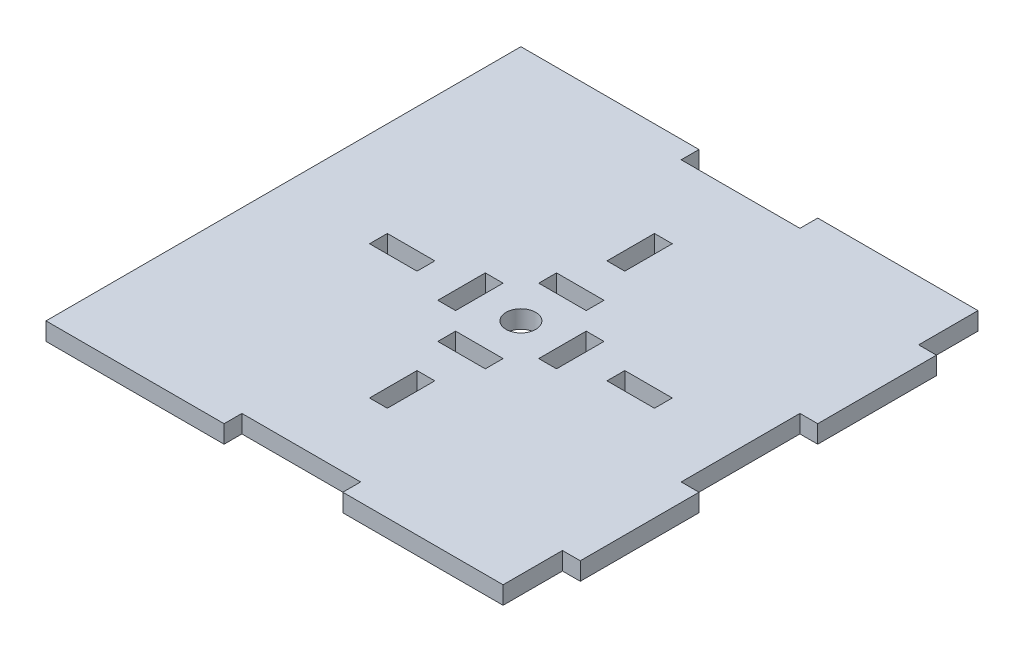
SolidWorks part; units mm, degrees
ref_plane "Alzado" through (0, 0, 0) normal (0, 0, 1) x (1, 0, 0)
ref_plane "Planta" through (0, 0, 0) normal (0, 1, 0) x (1, 0, 0)
ref_plane "Vista lateral" through (0, 0, 0) normal (1, 0, 0) x (0, 0, -1)
sketch "Croquis1" plane through (0, 0, 0) normal (0, 1, 0) x (1, 0, 0)
  line L0 (0, 0) -> (0, 10) construction
  line L1 (-40, 40) -> (-10, 40)
  line L2 (-40, 40) -> (-40, -40)
  line L3 (-40, -40) -> (-10, -40)
  line L4 (37, 30) -> (40, 30)
  line L5 (-40, 40) -> (40, -40) construction
  line L6 (-40, -40) -> (40, 40) construction
  line L7 (0, 10) -> (-4, 10)
  line L8 (-4, 10) -> (-4, 7)
  line L9 (-4, 7) -> (4, 7)
  line L10 (4, 7) -> (4, 10)
  line L11 (4, 10) -> (0, 10)
  line L12 (7, 4) -> (7, -4)
  line L13 (7, -4) -> (10, -4)
  line L14 (10, -4) -> (10, 0)
  line L15 (10, 0) -> (10, 4)
  line L16 (10, 4) -> (7, 4)
  line L17 (4, -7) -> (-4, -7)
  line L18 (-4, -7) -> (-4, -10)
  line L19 (-4, -10) -> (0, -10)
  line L20 (0, -10) -> (4, -10)
  line L21 (4, -10) -> (4, -7)
  line L22 (-7, -4) -> (-7, 4)
  line L23 (-7, 4) -> (-10, 4)
  line L24 (-10, 4) -> (-10, 0)
  line L25 (-10, 0) -> (-10, -4)
  line L26 (-10, -4) -> (-7, -4)
  line L27 (10, 0) -> (30, 0) construction
  line L28 (20, 0) -> (20, 1.5) construction
  line L29 (20, 1.5) -> (16, 1.5)
  line L30 (16, 1.5) -> (16, -1.5)
  line L31 (16, -1.5) -> (24, -1.5)
  line L32 (24, -1.5) -> (24, 1.5)
  line L33 (24, 1.5) -> (20, 1.5)
  line L34 (1.5, -20) -> (1.5, -16)
  line L35 (1.5, -24) -> (1.5, -20)
  line L36 (1.5, -16) -> (-1.5, -16)
  line L37 (-1.5, -16) -> (-1.5, -24)
  line L38 (-1.5, -24) -> (1.5, -24)
  line L39 (-20, -1.5) -> (-16, -1.5)
  line L40 (-24, -1.5) -> (-20, -1.5)
  line L41 (-16, -1.5) -> (-16, 1.5)
  line L42 (-16, 1.5) -> (-24, 1.5)
  line L43 (-24, 1.5) -> (-24, -1.5)
  line L44 (-1.5, 20) -> (-1.5, 16)
  line L45 (-1.5, 24) -> (-1.5, 20)
  line L46 (-1.5, 16) -> (1.5, 16)
  line L47 (1.5, 16) -> (1.5, 24)
  line L48 (1.5, 24) -> (-1.5, 24)
  line L49 (10, -40) -> (37, -40)
  line L50 (37, -10) -> (37, 10)
  line L51 (40, 30) -> (40, 10)
  line L52 (40, 10) -> (37, 10)
  line L54 (37, 30) -> (37, 40)
  line L55 (37, -10) -> (40, -10)
  line L56 (40, -30) -> (37, -30)
  line L57 (37, -30) -> (37, -40)
  line L58 (0, 37) -> (-10, 37)
  line L59 (0, 37) -> (10, 37)
  line L60 (10, 37) -> (10, 40)
  line L61 (-10, 37) -> (-10, 40)
  line L62 (10, 40) -> (37, 40)
  line L63 (-10, -37) -> (-10, -40)
  line L64 (10, -37) -> (10, -40)
  line L65 (0, -37) -> (10, -37)
  line L66 (0, -37) -> (-10, -37)
  line L67 (40, -10) -> (40, -30)
  circle A0 centre (0, 0) radius 2.5
  point P0 (0, 0)
  point P30 (0, 0)
  point P53 (0, 0)
  dimension "D14" = 5
  dimension "D1" = 80
  dimension "D2" = 80
  dimension "D3" = 10
  dimension "D4" = 4
  dimension "D5" = 3
  dimension "D6" = 8
  dimension "D8" = 20
  dimension "D9" = 1.5
  dimension "D10" = 4
  dimension "D11" = 3
  dimension "D12" = 8
  dimension "D16" = 10
  dimension "D17" = 10
  dimension "D7" = 4
  dimension "D13" = 4
extrude "Saliente-Extruir1" add sketch "Croquis1" along normal blind 3
